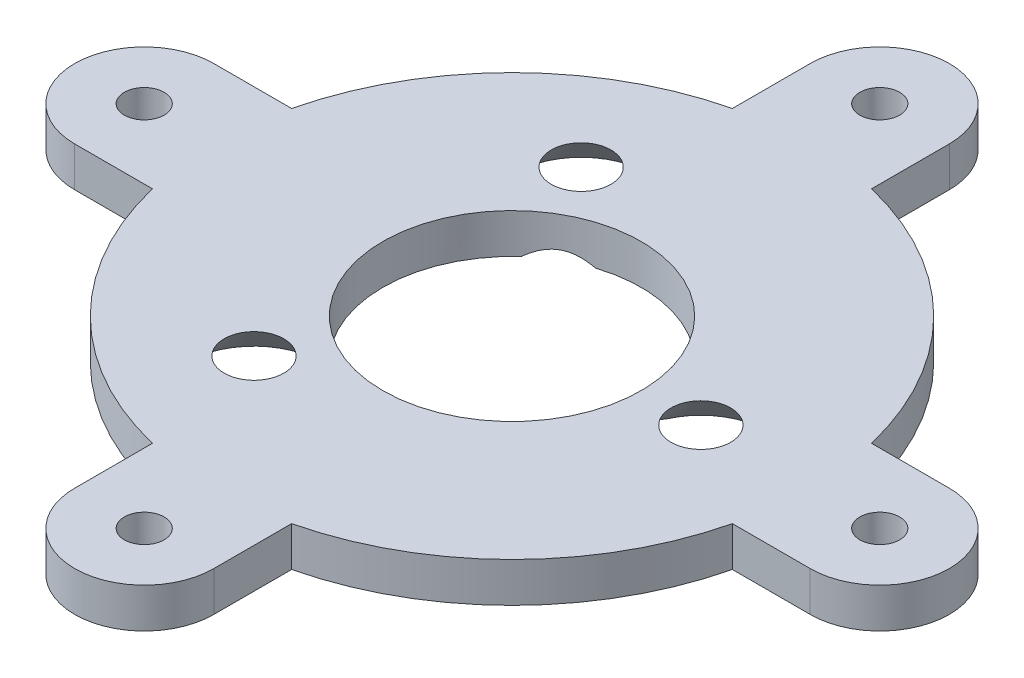
SolidWorks part; units mm, degrees
material "Thornel Mat VMA"
ref_plane "前视基准面" through (0, 0, 0) normal (0, 0, 1) x (1, 0, 0)
ref_plane "上视基准面" through (0, 0, 0) normal (0, 1, 0) x (1, 0, 0)
ref_plane "右视基准面" through (0, 0, 0) normal (1, 0, 0) x (0, 0, -1)
sketch "草图2" plane through (0, 0, 0) normal (0, 1, 0) x (1, 0, 0)
  line L0 (0, 36.746) -> (0, -40.7507) construction
  line L1 (-46.0543, 0) -> (43.2401, 0) construction
  circle A0 centre (0, 0) radius 6.5
  circle A1 centre (0, 0) radius 15
  circle A2 centre (9.5, 0) radius 1.5
  circle A3 centre (-4.75, -8.2272) radius 1.5
  circle A4 centre (-4.75, 8.2272) radius 1.5
  dimension "D1" = 13
  dimension "D2" = 9.5
  dimension "D3" = 3
  dimension "D5" = 30
  dimension "D4" = 3
extrude "凸台-拉伸1" add sketch "草图2" along normal blind 2
chamfer "倒角1" distance 2 angle 44 3 edges at (9.5, 0, 1.5) (-4.75, 0, 9.7272) (-4.75, 0, -6.7272) first distance on face at (9.5, 2, 1.5) first distance on face at (-4.75, 2, 9.7272) first distance on face at (-4.75, 2, -6.7272)
sketch "草图3" plane through (0, 0, 0) normal (0, 1, 0) x (1, 0, 0)
  line L0 (-25.2553, 0) -> (0, 0) construction
  line L1 (-18.5, -3.5) -> (-14.586, -3.5)
  line L2 (-18.5, 3.5) -> (-14.586, 3.5)
  line L7 (-3.5, 18.5) -> (-3.5, 14.586)
  line L8 (3.5, 18.5) -> (3.5, 14.586)
  line L9 (18.5, 3.5) -> (14.586, 3.5)
  line L10 (18.5, -3.5) -> (14.586, -3.5)
  line L11 (3.5, -18.5) -> (3.5, -14.586)
  line L12 (-3.5, -18.5) -> (-3.5, -14.586)
  circle A0 centre (-18.5, 0) radius 1
  arc A1 (-18.5, 3.5) -> (-18.5, -3.5) centre (-18.5, 0) ccw
  circle A2 centre (0, 0) radius 15 construction
  arc A3 (-14.586, -3.5) -> (-14.586, 3.5) centre (0, 0) cw
  arc A4 (-18.5, -3.5) -> (-15, 0) centre (-18.5, 0) ccw construction
  arc A5 (-15, 0) -> (-18.5, 3.5) centre (-18.5, 0) ccw construction
  circle A12 centre (0, 18.5) radius 1
  arc A13 (3.5, 18.5) -> (-3.5, 18.5) centre (0, 18.5) ccw
  arc A14 (-3.5, 14.586) -> (3.5, 14.586) centre (0, 0) cw
  arc A15 (-3.5, 18.5) -> (0, 15) centre (0, 18.5) ccw construction
  arc A16 (0, 15) -> (3.5, 18.5) centre (0, 18.5) ccw construction
  circle A17 centre (18.5, 0) radius 1
  arc A18 (18.5, -3.5) -> (18.5, 3.5) centre (18.5, 0) ccw
  arc A19 (14.586, 3.5) -> (14.586, -3.5) centre (0, 0) cw
  arc A20 (18.5, 3.5) -> (15, 0) centre (18.5, 0) ccw construction
  arc A21 (15, 0) -> (18.5, -3.5) centre (18.5, 0) ccw construction
  circle A22 centre (0, -18.5) radius 1
  arc A23 (-3.5, -18.5) -> (3.5, -18.5) centre (0, -18.5) ccw
  arc A24 (3.5, -14.586) -> (-3.5, -14.586) centre (0, 0) cw
  arc A25 (3.5, -18.5) -> (0, -15) centre (0, -18.5) ccw construction
  arc A26 (0, -15) -> (-3.5, -18.5) centre (0, -18.5) ccw construction
  dimension "D1" = 2
  dimension "D2" = 15
  dimension "D3" = 7
  dimension "D4" = 4
extrude "凸台-拉伸2" add sketch "草图3" along normal blind 2
